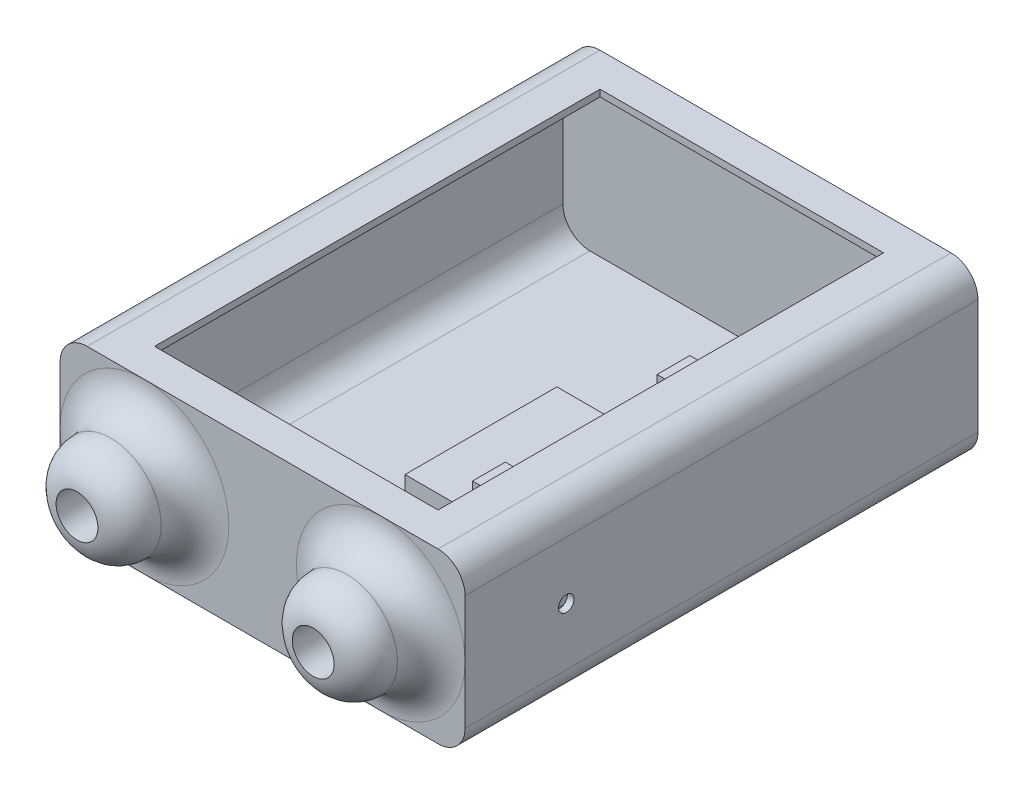
SolidWorks part; units mm, degrees
material "PLA Aero Bambu"
ref_plane "Front Plane" through (0, 0, 0) normal (0, 0, 1) x (1, 0, 0)
ref_plane "Top Plane" through (0, 0, 0) normal (0, 1, 0) x (1, 0, 0)
ref_plane "Right Plane" through (0, 0, 0) normal (1, 0, 0) x (0, 0, -1)
sketch "Sketch1" plane through (0, 0, 0) normal (0, 0, 1) x (1, 0, 0)
  line L1 (-30, 12.5) -> (30, 12.5)
  line L2 (-30, 12.5) -> (-30, -12.5)
  line L3 (-30, -12.5) -> (30, -12.5)
  line L4 (30, 12.5) -> (30, -12.5)
  line L5 (-30, 12.5) -> (30, -12.5) construction
  line L6 (-30, -12.5) -> (30, 12.5) construction
  point P0 (0, 0)
  dimension "D1" = 25
  dimension "D2" = 60
extrude "Boss-Extrude1" add sketch "Sketch1" against normal blind 1
sketch "Sketch2" plane through (0, 0, -1) normal (0, 0, -1) x (-1, 0, 0)
  line L0 (-30, 12.5) -> (-30, -12.5)
  line L1 (30, -12.5) -> (-30, -12.5) construction
  line L2 (-30, -12.5) -> (30, -12.5)
  line L3 (30, -12.5) -> (30, 12.5)
  line L4 (30, 12.5) -> (-30, 12.5)
  line L5 (29, 11.5) -> (-29, 11.5)
  line L6 (-29, 11.5) -> (-29, -11.5)
  line L7 (-29, -11.5) -> (29, -11.5)
  line L8 (29, -11.5) -> (29, 11.5)
  dimension "D1" = 1
extrude "Boss-Extrude2" add sketch "Sketch2" along normal blind 75
fillet "Fillet2" radius 4 8 edges at (30, 12.5, -38) (30, -12.5, -38) (-30, -12.5, -38) (-30, 12.5, -38) (-29, -11.5, -38.5) (-29, 11.5, -38.5) (29, 11.5, -38.5) (29, -11.5, -38.5)
sketch "Sketch4" plane through (0, 0, 0) normal (0, 0, 1) x (1, 0, 0)
  line L0 (-17.5, 0) -> (17.5, 0) construction
  circle A0 centre (-17.5, 0) radius 7.5
  circle A1 centre (-17.5, 0) radius 3.1
  circle A2 centre (17.5, 0) radius 3.1
  circle A3 centre (17.5, 0) radius 7.5
  point P5 (0, 0)
  dimension "D1" = 6.2
  dimension "D2" = 15
  dimension "D3" = 35
extrude "Boss-Extrude3" add sketch "Sketch4" along normal blind 10
fillet "Fillet3" radius 5 4 edges at (-10, 0, 0) (-10, 0, 10) (25, 0, 10) (25, 0, 0)
sketch "Sketch18" plane through (0, 0, 0) normal (0, 0, 1) x (1, 0, 0)
  circle A0 centre (-17.5, 0) radius 2
  circle A1 centre (17.5, 0) radius 2
  dimension "D1" = 4
extrude "Cut-Extrude6" cut sketch "Sketch18" against normal up to surface (1 mm away) up to face at (0, 0, -1)
sketch "Sketch5" plane through (30, 0, 0) normal (1, 0, 0) x (0, 0, -1)
  circle A0 centre (15, 0) radius 1.15
  point P5 (0, 0)
  point P6 (0, 0)
  point P7 (0, 0)
  dimension "D1" = 2.3
  dimension "D2" = 15
extrude "Cut-Extrude1" cut sketch "Sketch5" against normal through all contours A0
sketch "Sketch10" plane through (0, -11.5, 0) normal (0, 1, 0) x (1, 0, 0)
  line L0 (17.5, 0) -> (-17.5, 0) construction
  line L4 (26, 0) -> (26, 76) construction
  line L6 (-3.9968, 47.6018) -> (18.48, 47.6018)
  line L7 (-3.9968, 47.6018) -> (-3.9968, 25.1)
  line L8 (-3.9968, 25.1) -> (18.48, 25.1)
  line L9 (18.48, 47.6018) -> (18.48, 25.1)
  point P4 (0, 0)
  point P15 (0, 0)
  dimension "D1" = 25.1
  dimension "D2" = 7.52
  dimension "D3" = 22.5018
  dimension "D4" = 22.4768
extrude "Boss-Extrude4" add sketch "Sketch10" along normal blind 6
sketch "Sketch12" plane through (0, -11.5, 0) normal (0, 1, 0) x (1, 0, 0)
  line L5 (25, 1) -> (25, 76) construction
  line L10 (10.83, 25.1335) -> (13.33, 25.1335)
  line L12 (10.83, 25.1335) -> (10.83, 20.275)
  line L13 (10.83, 20.275) -> (13.33, 20.275)
  line L14 (13.33, 25.1335) -> (13.33, 20.275)
  line L15 (10.83, 47.6165) -> (13.33, 47.6165)
  line L16 (10.83, 47.6165) -> (10.83, 52.475)
  line L17 (10.83, 52.475) -> (13.33, 52.475)
  line L18 (13.33, 47.6165) -> (13.33, 52.475)
  point P25 (0, 0)
  dimension "D1" = 4.8585
  dimension "D4" = 2.5
  dimension "D5" = 11.67
  dimension "D6" = 22.483
  dimension "D7" = 20.275
extrude "Boss-Extrude5" add sketch "Sketch12" along normal blind 15
sketch "Sketch13" plane through (13.33, 0, 0) normal (1, 0, 0) x (0, 0, -1)
  circle A0 centre (22.7042, 0) radius 1.35
  circle A1 centre (50.0458, 0) radius 1.35
  point P2 (0, 0)
  point P3 (0, 0)
  point P6 (0, 0)
  dimension "D2" = 2.7
  dimension "D3" = 2.7
  dimension "D4" = 27.3415
  dimension "D1" = 22.7042
extrude "Cut-Extrude3" cut sketch "Sketch13" against normal blind 12
sketch "Sketch15" plane through (0, -11.5, 0) normal (0, 1, 0) x (1, 0, 0)
  line L0 (29, 76) -> (29, 1) construction
  line L1 (19, 18) -> (24, 18)
  line L2 (19, 18) -> (19, 12)
  line L3 (19, 12) -> (24, 12)
  line L4 (24, 18) -> (24, 12)
  line L5 (19, 12) -> (24, 18) construction
  line L6 (24, 12) -> (19, 18) construction
  line L8 (25, 1) -> (-25, 1) construction
  point P6 (21.5, 15)
  dimension "D1" = 5
  dimension "D2" = 6
  dimension "D3" = 5
  dimension "D4" = 14
extrude "Boss-Extrude6" add sketch "Sketch15" along normal blind 14
sketch "Sketch16" plane through (24, 0, 0) normal (1, 0, 0) x (0, 0, -1)
  circle A0 centre (15, 0) radius 1.25
extrude "Cut-Extrude4" cut sketch "Sketch16" against normal blind 5
sketch "Sketch19" plane through (0, 12.5, 0) normal (0, 1, 0) x (1, 0, 0)
  line L0 (-26, 76) -> (-26, 0) construction
  line L1 (-21, 5) -> (21, 5)
  line L2 (-21, 5) -> (-21, 71)
  line L3 (-21, 71) -> (21, 71)
  line L4 (21, 5) -> (21, 71)
  line L5 (17.5, 0) -> (-17.5, 0) construction
  line L6 (-26, 76) -> (26, 76) construction
  point P6 (0, 5)
  dimension "D1" = 5
  dimension "D2" = 5
  dimension "D3" = 5
extrude "Cut-Extrude7" cut sketch "Sketch19" against normal up to surface (1 mm away) up to face at (0, 11.5, -38.5)
sketch "Sketch17" [suppressed] plane through (0, 0, -76) normal (0, 0, -1) x (-1, 0, 0)
  line L0 (20, 8.5) -> (-20, 8.5)
split "Split1" [suppressed] bodies to split 114
sketch "Sketch20" plane through (0, 0, -76) normal (0, 0, -1) x (-1, 0, 0)
  line L0 (-25, 11.5) -> (25, 11.5)
  line L1 (29, 7.5) -> (29, -7.5)
  line L2 (-25, -11.5) -> (25, -11.5)
  line L3 (-29, 7.5) -> (-29, -7.5)
  arc A0 (-29, 7.5) -> (-25, 11.5) centre (-25, 7.5) cw
  arc A1 (25, 11.5) -> (29, 7.5) centre (25, 7.5) cw
  arc A2 (25, -11.5) -> (29, -7.5) centre (25, -7.5) ccw construction
  arc A3 (25, -11.5) -> (29, -7.5) centre (25, -7.5) ccw construction
  arc A4 (29, -7.5) -> (25, -11.5) centre (25, -7.5) cw
  arc A5 (-25, -11.5) -> (-29, -7.5) centre (-25, -7.5) cw
extrude "Boss-Extrude7" add sketch "Sketch20" against normal blind 2.5
